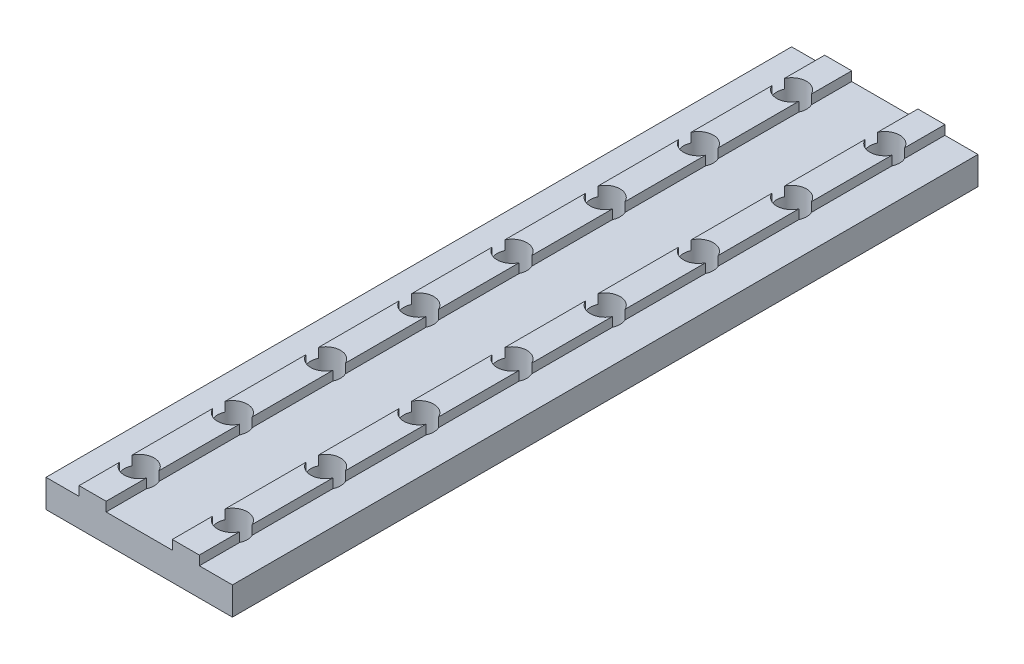
SolidWorks part; units mm, degrees
ref_plane "Front Plane" through (0, 0, 0) normal (0, 0, 1) x (1, 0, 0)
ref_plane "Top Plane" through (0, 0, 0) normal (0, 1, 0) x (1, 0, 0)
ref_plane "Right Plane" through (0, 0, 0) normal (1, 0, 0) x (0, 0, -1)
sketch "Esquisse1" plane through (0, 0, 0) normal (0, 0, 1) x (1, 0, 0)
  line L0 (-5, 0) -> (-5, 3)
  line L1 (-5, 3) -> (-1.45, 3)
  line L2 (-1.45, 3) -> (-1.45, 4)
  line L3 (-1.45, 4) -> (1.45, 4)
  line L4 (1.45, 4) -> (1.45, 3)
  line L5 (1.45, 3) -> (5, 3)
  line L6 (5, 3) -> (5, 0)
  line L7 (5, 0) -> (-5, 0)
  point P11 (0, 0)
  dimension "D1" = 10
  dimension "D2" = 3
  dimension "D3" = 1
  dimension "D4" = 2.9
  dimension "D5" = 3.55
extrude "Main" add sketch "Esquisse1" along normal blind 20
sketch "Esquisse2" plane through (0, 4, 0) normal (0, 1, 0) x (1, 0, 0)
  line L0 (0, -2.2) -> (0, 2.2) construction
  line L1 (-1.45, 0) -> (-5, 0) construction
  line L2 (-1.45, -20) -> (-5, -20) construction
  circle A0 centre (0, -5) radius 1.6
  circle A1 centre (0, -15) radius 1.6
  dimension "D2" = 5
  dimension "D3" = 3.2
  dimension "D1" = 5
extrude "TopHole" cut sketch "Esquisse2" against normal through all
ref_axis "Axe1" through (-5.5, 0, 0) along (1, 0, 0)
pattern_linear "Répétition linéaire1" count 4 spacing 20 along (0, 0, 1) count 2 spacing 10 along (-1, 0, 0) of "TopHole", "Main"
